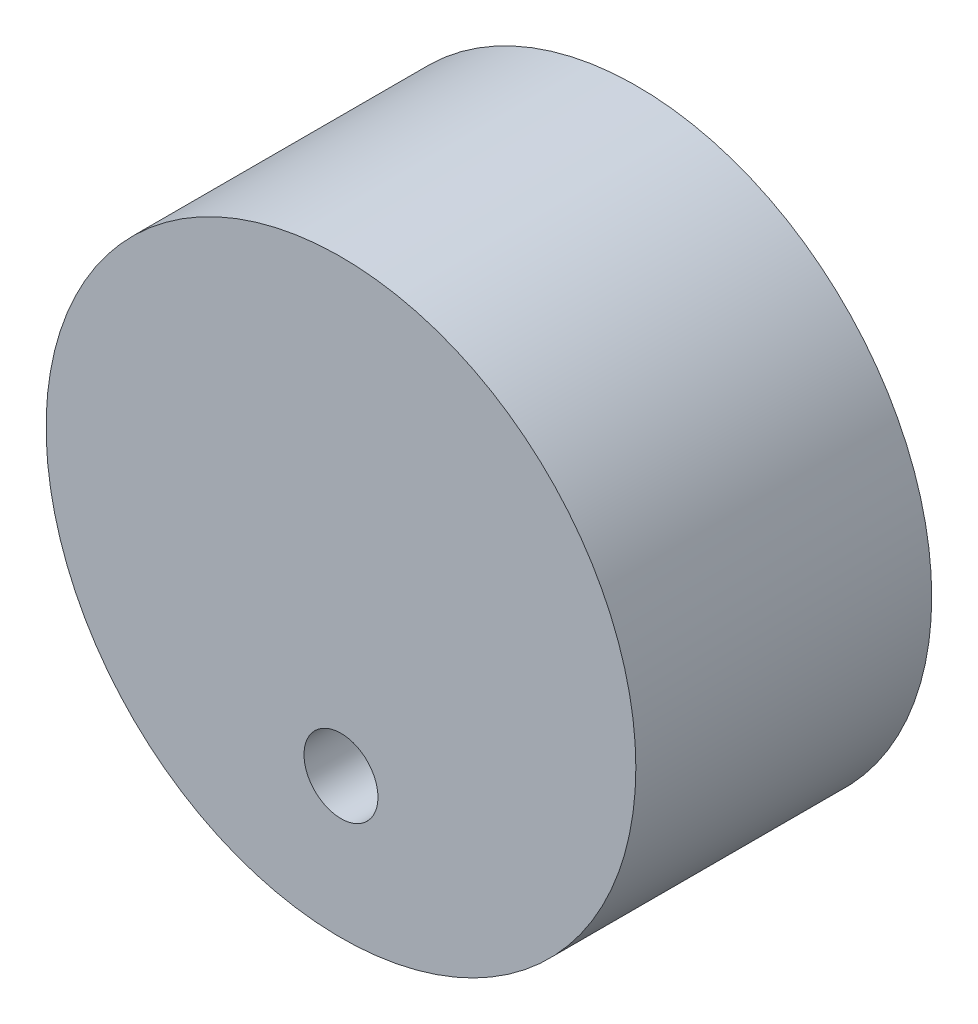
SolidWorks part; units mm, degrees
ref_plane "Front Plane" through (0, 0, 0) normal (0, 0, 1) x (1, 0, 0)
ref_plane "Top Plane" through (0, 0, 0) normal (0, 1, 0) x (1, 0, 0)
ref_plane "Right Plane" through (0, 0, 0) normal (1, 0, 0) x (0, 0, -1)
sketch "Sketch1" plane through (0, 0, 0) normal (0, 0, 1) x (1, 0, 0)
  circle A0 centre (0, 0) radius 25.3146
extrude "Boss-Extrude1" add sketch "Sketch1" along normal blind 25.4
sketch "Sketch2" plane through (0, 0, 25.4) normal (0, 0, 1) x (1, 0, 0)
  circle A0 centre (0, -13.2788) radius 3.175
  dimension "D1" = 6.35
extrude "Cut-Extrude1" cut sketch "Sketch2" against normal blind 25.4
